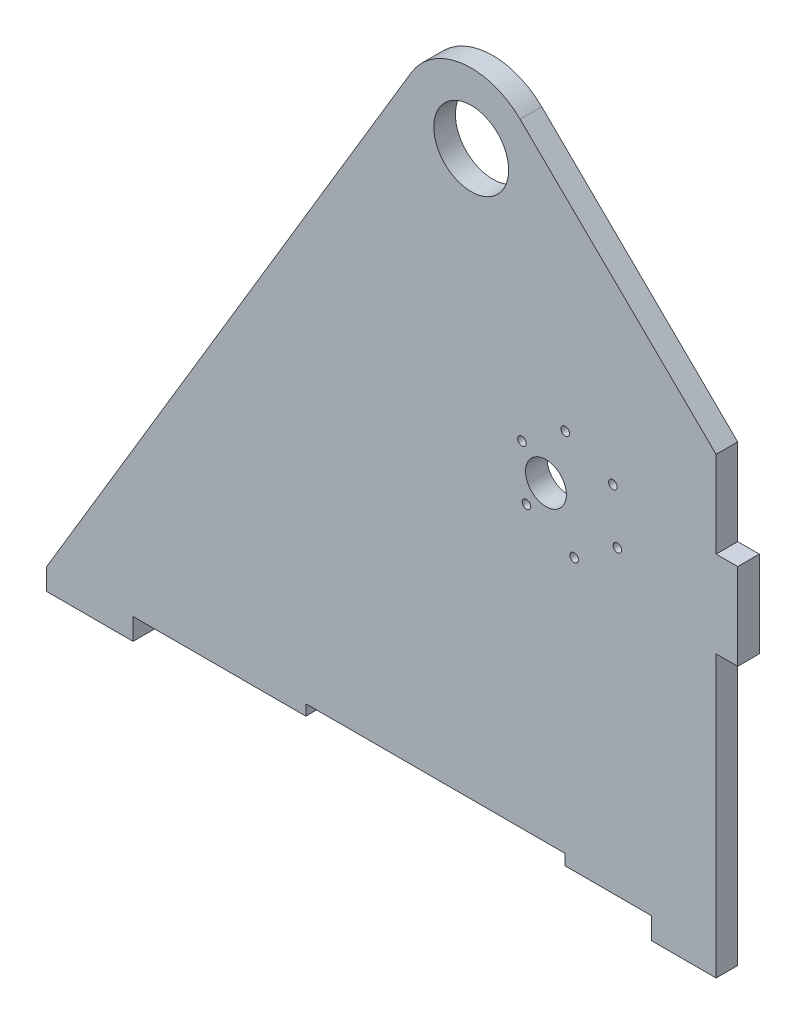
SolidWorks part; units mm, degrees
ref_plane "Front Plane" through (0, 0, 0) normal (0, 0, 1) x (1, 0, 0)
ref_plane "Top Plane" through (0, 0, 0) normal (0, 1, 0) x (1, 0, 0)
ref_plane "Right Plane" through (0, 0, 0) normal (1, 0, 0) x (0, 0, -1)
sketch "Sketch2" plane through (0, 0, 0) normal (0, 0, 1) x (1, 0, 0)
  line L0 (1566.672, 2.5421) -> (1649.222, 2.5421) construction
  line L1 (1592.072, 2.5421) -> (1642.872, 2.5421)
  line L2 (1566.672, 2.5421) -> (1673.8864, 181.9515)
  line L4 (1642.872, 2.5421) -> (1642.872, 5.7171)
  line L6 (1566.672, 2.5421) -> (1566.672, -3.8079)
  line L7 (1566.672, -3.8079) -> (1592.072, -3.8079)
  line L8 (1592.072, 2.5421) -> (1592.072, -3.8079)
  line L13 (1642.872, 5.7171) -> (1719.072, 5.7171)
  line L14 (1719.072, 5.7171) -> (1719.072, 2.5421)
  line L16 (1719.072, 2.5421) -> (1744.472, 2.5421)
  line L17 (1566.672, -33.6061) -> (1769.872, -33.6061) construction
  line L18 (1744.472, 2.5421) -> (1744.472, -3.8079)
  line L19 (1744.472, -3.8079) -> (1763.522, -3.8079)
  line L20 (1763.522, -3.8079) -> (1763.522, 78.7421)
  line L22 (1763.522, 129.5421) -> (1705.8766, 186.0765)
  line L23 (1763.522, 104.1421) -> (1763.522, 129.5421)
  line L24 (1763.522, 104.1421) -> (1769.872, 104.1421)
  line L26 (1763.522, 78.7421) -> (1769.872, 78.7421)
  line L27 (1769.872, 104.1421) -> (1769.872, 78.7421)
  arc A0 (1705.8766, 186.0765) -> (1673.8864, 181.9515) centre (1691.5051, 171.4226) ccw
  circle A1 centre (1691.5051, 171.4226) radius 11 construction
  circle A2 centre (1691.5051, 171.4226) radius 4 construction
  circle A3 centre (1691.5051, 171.4226) radius 11
  dimension "D3" = 22
  dimension "D4" = 9.525
  dimension "D5" = 8
  dimension "D6" = 22
  dimension "D1" = 168.8805
  dimension "D2" = 124.8331
  dimension "D7" = 6.35
  dimension "D8" = 25.4
  dimension "D9" = 19.05
  dimension "D10" = 6.35
  dimension "D11" = 44.45
  dimension "D12" = 203.2
  dimension "D13" = 76.2
  dimension "D14" = 3.175
  dimension "D15" = 133.35
  dimension "D16" = 6.35
  dimension "D17" = 25.4
  dimension "D18" = 25.4
extrude "Boss-Extrude1" add sketch "Sketch2" along normal blind 6.35
sketch "Sketch4" plane through (0, 0, 6.35) normal (0, 0, 1) x (1, 0, 0)
  line L0 (1673.3123, 156.2334) -> (1577.5737, -3.9728)
  line L1 (1691.5051, 171.4226) -> (1750.822, 113.2489)
  line L2 (1684.7881, 175.4367) -> (1577.5737, -3.9728) construction
  line L3 (1590.9538, 18.4171) -> (1750.822, 18.4171)
  line L4 (1686.3016, 73.3904) -> (1617.2071, 143.6449) construction
  line L7 (1681.7742, 68.9378) -> (1612.6797, 139.1923)
  line L10 (1690.8289, 77.843) -> (1621.7344, 148.0975)
  line L13 (1566.672, 2.5421) -> (1566.672, -3.8079)
  line L14 (1566.672, -3.8079) -> (1592.072, -3.8079)
  line L15 (1592.072, -3.8079) -> (1592.072, 2.5421)
  line L16 (1592.072, 2.5421) -> (1642.872, 2.5421)
  line L17 (1642.872, 2.5421) -> (1642.872, 5.7171)
  line L18 (1642.872, 5.7171) -> (1719.072, 5.7171)
  line L19 (1719.072, 5.7171) -> (1719.072, 2.5421)
  line L20 (1719.072, 2.5421) -> (1744.472, 2.5421)
  line L21 (1744.472, -3.8079) -> (1763.522, -3.8079)
  line L22 (1744.472, 2.5421) -> (1744.472, -3.8079)
  line L23 (1719.072, 2.5421) -> (1744.472, 2.5421)
  line L24 (1763.522, -3.8079) -> (1763.522, 78.7421)
  line L25 (1673.8864, 181.9515) -> (1566.672, 2.5421)
  line L26 (1566.672, 2.5421) -> (1566.672, -3.8079)
  line L27 (1566.672, -3.8079) -> (1592.072, -3.8079)
  line L28 (1592.072, -3.8079) -> (1592.072, 2.5421)
  line L29 (1592.072, 2.5421) -> (1642.872, 2.5421)
  line L30 (1642.872, 2.5421) -> (1642.872, 5.7171)
  line L31 (1642.872, 5.7171) -> (1719.072, 5.7171)
  line L32 (1719.072, 5.7171) -> (1719.072, 2.5421)
  line L34 (1744.472, -3.8079) -> (1763.522, -3.8079)
  line L35 (1744.472, 2.5421) -> (1744.472, -3.8079)
  line L38 (1673.8864, 181.9515) -> (1566.672, 2.5421)
  line L39 (1686.3016, 73.3904) -> (1776.688, 147.3217) construction
  line L42 (1682.2812, 78.3056) -> (1772.6676, 152.2368)
  line L45 (1690.3219, 68.4752) -> (1780.7084, 142.4065)
  line L46 (1686.3016, 73.3904) -> (1535.3984, -21.6576) construction
  line L47 (1750.822, 113.2489) -> (1750.822, 18.4171)
  line L48 (1689.6858, 68.0174) -> (1538.7827, -27.0307)
  line L49 (1682.9173, 78.7634) -> (1532.0142, -16.2846)
  line L50 (1686.3016, 73.3904) -> (1767.8024, 12.8123) construction
  line L51 (1690.0896, 78.4868) -> (1771.5905, 17.9087)
  line L52 (1682.5135, 68.294) -> (1764.0144, 7.7159)
  line L53 (1691.5051, 171.4226) -> (1681.8948, -9.6316) construction
  line L54 (1697.8462, 171.086) -> (1688.2358, -9.9682)
  line L55 (1685.1641, 171.7592) -> (1675.5537, -9.2951)
  line L60 (1763.522, -3.8079) -> (1763.522, 78.7421)
  line L61 (1763.522, 129.5421) -> (1705.8766, 186.0765)
  line L62 (1763.522, 129.5421) -> (1705.8766, 186.0765)
  line L68 (1763.522, 78.7421) -> (1769.872, 78.7421)
  line L69 (1763.522, 78.7421) -> (1769.872, 78.7421)
  line L70 (1769.872, 78.7421) -> (1769.872, 104.1421)
  line L71 (1769.872, 78.7421) -> (1769.872, 104.1421)
  line L72 (1769.872, 104.1421) -> (1763.522, 104.1421)
  line L73 (1769.872, 104.1421) -> (1763.522, 104.1421)
  line L74 (1763.522, 104.1421) -> (1763.522, 129.5421)
  line L75 (1763.522, 104.1421) -> (1763.522, 129.5421)
  arc A1 (1705.8766, 186.0765) -> (1673.8864, 181.9515) centre (1691.5051, 171.4226) ccw
  arc A2 (1705.8766, 186.0765) -> (1673.8864, 181.9515) centre (1691.5051, 171.4226) ccw
  circle A4 centre (1691.5051, 171.4226) radius 23.7
  circle A5 centre (1691.5051, 171.4226) radius 23.7
  arc A14 (1681.7742, 68.9378) -> (1690.8289, 77.843) centre (1686.3016, 73.3904) ccw
  arc A15 (1621.7344, 148.0975) -> (1612.6797, 139.1923) centre (1617.2071, 143.6449) ccw
  arc A16 (1682.2812, 78.3056) -> (1690.3219, 68.4752) centre (1686.3016, 73.3904) ccw
  arc A17 (1780.7084, 142.4065) -> (1772.6676, 152.2368) centre (1776.688, 147.3217) ccw
  arc A18 (1689.6858, 68.0174) -> (1682.9173, 78.7634) centre (1686.3016, 73.3904) ccw
  arc A19 (1532.0142, -16.2846) -> (1538.7827, -27.0307) centre (1535.3984, -21.6576) ccw
  arc A20 (1690.0896, 78.4868) -> (1682.5135, 68.294) centre (1686.3016, 73.3904) ccw
  arc A21 (1764.0144, 7.7159) -> (1771.5905, 17.9087) centre (1767.8024, 12.8123) ccw
  arc A22 (1697.8462, 171.086) -> (1685.1641, 171.7592) centre (1691.5051, 171.4226) ccw
  arc A23 (1675.5537, -9.2951) -> (1688.2358, -9.9682) centre (1681.8948, -9.6316) ccw
  point P15 (1651.7543, 108.5176)
  point P28 (1731.4948, 110.356)
  point P35 (1610.85, 25.8664)
  point P42 (1727.052, 43.1013)
  point P50 (1686.6999, 80.8955)
  dimension "D6" = 6.35
  dimension "D4" = 12.7
  dimension "D5" = 12.7
  dimension "D1" = 0
  dimension "D2" = 12.7
  dimension "D3" = 12.7
extrude "Cut-Extrude1" [suppressed] cut sketch "Sketch4" against normal through all contours L49 L7 L0 | A5 L0 L10 L55 | A5 L54 L42 L1 | L45 L51 L47 L1 | L52 L54 L3 | L55 L48 L3
fillet "Fillet1" [suppressed] radius 2.54
sketch "Sketch5" plane through (0, 0, 0) normal (0, 0, -1) x (-1, 0, 0)
  circle A0 centre (-1734.4915, 91.2387) radius 1.25 construction
  circle A2 centre (-1721.7757, 82.3754) radius 1.25 construction
  circle A3 centre (-1707.742, 88.9559) radius 1.25 construction
  circle A4 centre (-1733.1735, 106.6826) radius 1.25 construction
  circle A5 centre (-1719.1398, 113.2631) radius 1.25 construction
  circle A6 centre (-1706.424, 104.3998) radius 1.25 construction
  circle A7 centre (-1713.4831, 97.224) radius 6
  circle A8 centre (-1734.4915, 91.2387) radius 1.25
  circle A9 centre (-1721.7757, 82.3754) radius 1.25
  circle A10 centre (-1707.742, 88.9559) radius 1.25
  circle A11 centre (-1733.1735, 106.6826) radius 1.25
  circle A12 centre (-1719.1398, 113.2631) radius 1.25
  circle A13 centre (-1706.424, 104.3998) radius 1.25
  point P0 (-1718.5152, 100.4917)
  dimension "D1" = 6
extrude "Cut-Extrude2" cut sketch "Sketch5" against normal through all both and the other way through all
